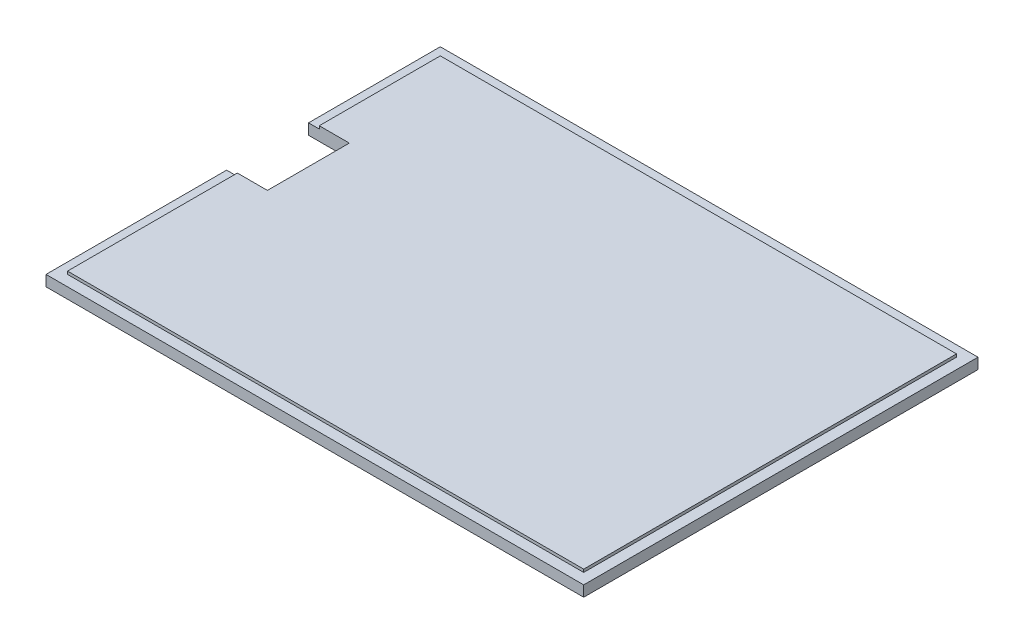
SolidWorks part; units mm, degrees
ref_plane "Front Plane" through (0, 0, 0) normal (0, 0, 1) x (1, 0, 0)
ref_plane "Top Plane" through (0, 0, 0) normal (0, 1, 0) x (1, 0, 0)
ref_plane "Right Plane" through (0, 0, 0) normal (1, 0, 0) x (0, 0, -1)
sketch "Sketch1" plane through (0, 0, 0) normal (0, 1, 0) x (1, 0, 0)
  line L0 (-375, 275) -> (375, 275)
  line L1 (-380, -280) -> (380, -280) construction
  line L2 (-380, -280) -> (-380, 280) construction
  line L3 (-380, 280) -> (380, 280) construction
  line L4 (380, -280) -> (380, 280) construction
  line L5 (-380, -280) -> (380, 280) construction
  line L6 (-380, 280) -> (380, -280) construction
  line L7 (375, -275) -> (375, 275)
  line L8 (-375, -275) -> (375, -275)
  line L9 (-375, -275) -> (-375, 275)
  point P0 (0, 0)
  dimension "D1" = 760
  dimension "D2" = 560
  dimension "D3" = 5
extrude "Boss-Extrude1" add sketch "Sketch1" along normal blind 19
sketch "Sketch2" plane through (0, 19, 0) normal (0, 1, 0) x (1, 0, 0)
  line L0 (375, 275) -> (-375, 275) construction
  line L5 (-370, 0) -> (370, 0) construction
  line L7 (-370, -270) -> (370, -270) construction
  line L8 (-370, -270) -> (-370, 270) construction
  line L9 (-370, 270) -> (370, 270) construction
  line L10 (370, -270) -> (370, 270) construction
  line L11 (-370, -270) -> (370, 270) construction
  line L12 (-370, 270) -> (370, -270) construction
  line L13 (375, -275) -> (375, 275) construction
  line L14 (0, 270) -> (0, -270) construction
  circle A1 centre (-370, 270) radius 1.5
  circle A2 centre (-185, 270) radius 1.5
  circle A3 centre (0, 270) radius 1.5
  circle A4 centre (185, 270) radius 1.5
  circle A5 centre (370, 270) radius 1.5
  circle A6 centre (-370, 90) radius 1.5
  circle A7 centre (-370, -90) radius 1.5
  circle A8 centre (-370, -270) radius 1.5
  circle A9 centre (370, -270) radius 1.5
  circle A10 centre (185, -270) radius 1.5
  circle A11 centre (0, -270) radius 1.5
  circle A12 centre (-185, -270) radius 1.5
  circle A13 centre (-370, -270) radius 1.5
  circle A14 centre (370, -90) radius 1.5
  circle A15 centre (370, 90) radius 1.5
  point P0 (0, 0)
  point P6 (0, 0)
  dimension "D1" = 3
  dimension "D2" = 5
  dimension "D3" = 5
  dimension "D4" = 5
  dimension "D5" = 4
extrude "Cut-Extrude1" [suppressed] cut sketch "Sketch2" against normal through all contours A1 | A2 | A3 | A4 | A5 | A15 | A14 | A9 | A10 | A11 | A12 | A8 | A7 | A6
sketch "Sketch3" plane through (0, 19, 0) normal (0, 1, 0) x (1, 0, 0)
  line L8 (-360, 260) -> (-360, -260)
  line L9 (-360, -260) -> (360, -260)
  line L10 (360, -260) -> (360, 260)
  line L11 (360, 260) -> (-360, 260)
  line L12 (-360, 260) -> (-360, -260)
  line L13 (-360, -260) -> (360, -260)
  line L14 (360, -260) -> (360, 260)
  line L15 (360, 260) -> (-360, 260)
  line L16 (-375, 275) -> (-375, -275)
  line L17 (-375, -275) -> (375, -275)
  line L18 (375, -275) -> (375, 275)
  line L19 (375, 275) -> (-375, 275)
  line L20 (-375, 275) -> (-375, -275)
  line L21 (-375, -275) -> (375, -275)
  line L22 (375, -275) -> (375, 275)
  line L23 (375, 275) -> (-375, 275)
  dimension "D1" = 15
  dimension "D2" = 0
extrude "Cut-Extrude2" cut sketch "Sketch3" against normal blind 4
sketch "Sketch4" plane through (0, 0, 0) normal (0, -1, 0) x (1, 0, 0)
  line L0 (-375, -275) -> (-375, 275) construction
  line L1 (-375, 23.0958) -> (-318.0734, 23.0958)
  line L2 (-375, 23.0958) -> (-375, -91.1675)
  line L3 (-375, -91.1675) -> (-318.0734, -91.1675)
  line L4 (-318.0734, 23.0958) -> (-318.0734, -91.1675)
extrude "Cut-Extrude3" cut sketch "Sketch4" against normal through all
equation "\"Crossbar_Width\"= 80mm"
equation "\"Vertical_Offset\"= \"Crossbar_Width\" / 2"
equation "\"Toolhead_Width\"= 100mm"
equation "\"Mechanical_Buffer\"= 30mm"
equation "\"Z_Interstitial\"= 100mm"
equation "\"Z_Interstitial_Sketch\"= \"Z_Interstitial\" + 1in"
